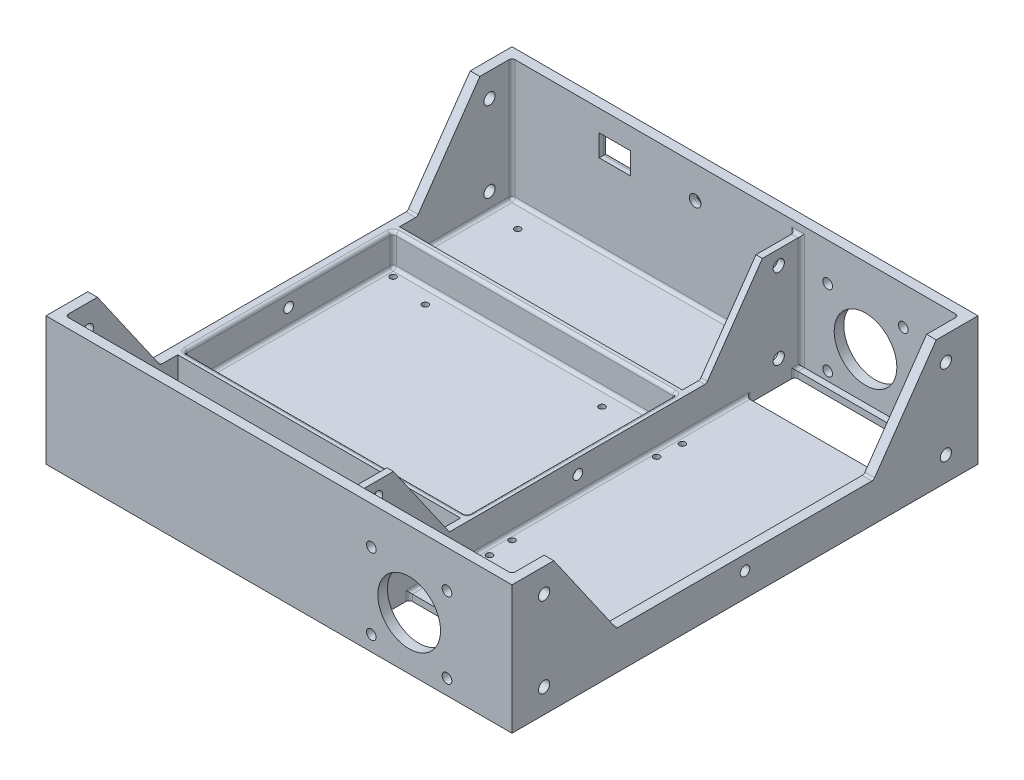
SolidWorks part; units mm, degrees
ref_plane "Спереди" through (0, 0, 0) normal (0, 0, 1) x (1, 0, 0)
ref_plane "Сверху" through (0, 0, 0) normal (0, 1, 0) x (1, 0, 0)
ref_plane "Справа" through (0, 0, 0) normal (1, 0, 0) x (0, 0, -1)
sketch "Эскиз1" plane through (0, 0, 0) normal (0, 1, 0) x (1, 0, 0)
  line L1 (-145, -145) -> (145, -145)
  line L2 (-145, -145) -> (-145, 145)
  line L3 (-145, 145) -> (145, 145)
  line L4 (145, -145) -> (145, 145)
  line L5 (0, 145) -> (0, -145) construction
  line L6 (-145, 0) -> (145, 0) construction
  point P0 (0, 0)
  dimension "D1" = 290
  dimension "D2" = 290
extrude "Бобышка-Вытянуть1" add sketch "Эскиз1" along normal blind 4
sketch "Эскиз2" plane through (0, 4, 0) normal (0, 1, 0) x (1, 0, 0)
  line L2 (145, 145) -> (145, 0.2395)
  line L5 (0, 0) -> (241.6766, 0) construction
  line L8 (145, -145) -> (145, 0.2395)
  line L11 (139, 139) -> (139, -139)
  line L13 (145, 145) -> (-145, 145) construction
  line L17 (145, 145) -> (-139, 145)
  line L18 (-139, 145) -> (-139, 139)
  line L19 (-139, 139) -> (139, 139)
  line L24 (-145, 145) -> (-145, -145) construction
  line L25 (-139, -139) -> (139, -139)
  line L30 (-139, -145) -> (-139, -139)
  line L35 (145, -145) -> (-139, -145)
  point P14 (139, 0)
  dimension "D1" = 6
  dimension "D3" = 6
  dimension "D9" = 6
extrude "Бобышка-Вытянуть2" add sketch "Эскиз2" along normal blind 76
sketch "Эскиз4" plane through (0, 4, 0) normal (0, 1, 0) x (1, 0, 0)
  line L0 (-145, -145) -> (-139, -145) construction
  line L1 (-145, 145) -> (-139, 145)
  line L2 (-145, 145) -> (-145, -145)
  line L3 (-145, -145) -> (-139, -145)
  line L4 (-139, 145) -> (-139, -145)
  dimension "D1" = 6
extrude "Бобышка-Вытянуть3" add sketch "Эскиз4" along normal up to surface (76 mm away) up to face at (1.5, 80, 0)
sketch "Эскиз17" plane through (0, 0, 145) normal (0, 0, 1) x (1, 0, 0)
  line L0 (81, 114.7773) -> (81, 33) construction
  line L1 (81, 33) -> (205.181, 33) construction
  line L2 (145, 80) -> (145, 0) construction
  line L3 (-145, 0) -> (145, 0) construction
  line L6 (57.45, 9.45) -> (104.55, 9.45) construction
  line L7 (57.45, 9.45) -> (57.45, 56.55) construction
  line L8 (57.45, 56.55) -> (104.55, 56.55) construction
  line L9 (104.55, 9.45) -> (104.55, 56.55) construction
  line L10 (81, 56.55) -> (81, 9.45) construction
  line L11 (57.45, 33) -> (104.55, 33) construction
  circle A0 centre (81, 33) radius 19.5
  circle A1 centre (57.45, 56.55) radius 3
  circle A4 centre (104.55, 56.55) radius 3
  circle A5 centre (104.55, 9.45) radius 3
  circle A6 centre (57.45, 9.45) radius 3
  dimension "D3" = 39
  dimension "D5" = 6
  dimension "D2" = 33
  dimension "D1" = 64
  dimension "D4" = 47.1
extrude "Вырез-Вытянуть12" cut sketch "Эскиз17" against normal through all both and the other way through all contours A0 | A1 | A4 | A5 | A6 region at (81, 33, 145) region at (57.45, 56.55, 145) region at (104.55, 56.55, 145) region at (104.55, 9.45, 145) region at (57.45, 9.45, 145)
sketch "Эскиз18" plane through (0, 4, 0) normal (0, 1, 0) x (1, 0, 0)
  line L0 (41, 0) -> (179.6266, 0) construction
  line L1 (-21, 118.2107) -> (-21, -110.4846) construction
  line L2 (145, -145) -> (145, 145) construction
  line L7 (37, -145) -> (41, -145)
  line L8 (37, -145) -> (37, 145)
  line L9 (37, 145) -> (41, 145)
  line L10 (41, -145) -> (41, 145)
  line L11 (39, 145) -> (39, -145) construction
  line L12 (37, 0) -> (41, 0) construction
  line L20 (145, 145) -> (-145, 145) construction
  point P16 (39, 0)
  dimension "D1" = 4
  dimension "D2" = 104
extrude "Бобышка-Вытянуть4" add sketch "Эскиз18" along normal blind 70
sketch "Эскиз19" plane through (145, 0, 0) normal (1, 0, 0) x (0, 0, -1)
  line L0 (0, 117.0161) -> (0, 24) construction
  line L1 (0, 24) -> (182.1669, 24) construction
  line L2 (-145, 0) -> (145, 0) construction
  line L3 (-80, 24) -> (80, 24)
  line L4 (80, 24) -> (119, 80)
  line L5 (-145, 80) -> (145, 80) construction
  line L6 (119, 80) -> (-119, 80)
  line L7 (145, 80) -> (145, 0) construction
  line L8 (-80, 24) -> (-119, 80)
  point P14 (0, 80)
  dimension "D1" = 24
  dimension "D2" = 26
  dimension "D3" = 160
extrude "Вырез-Вытянуть13" cut sketch "Эскиз19" against normal through all both and the other way through all
sketch "Эскиз14" plane through (0, 4, 0) normal (0, 1, 0) x (1, 0, 0)
  line L0 (81, 159.053) -> (81, -165.8467) construction
  line L2 (145, 145) -> (-145, 145) construction
  line L3 (41, 105) -> (121, 105)
  line L4 (41, 105) -> (41, 135)
  line L5 (41, 135) -> (121, 135)
  line L6 (121, 105) -> (121, 135)
  line L7 (81, 135) -> (81, 105) construction
  line L8 (41, 120) -> (121, 120) construction
  line L9 (0, 0) -> (180.733, 0) construction
  line L10 (41, -135) -> (121, -135)
  line L11 (121, -105) -> (121, -135)
  line L12 (41, -105) -> (121, -105)
  line L13 (41, -105) -> (41, -135)
  line L14 (145, 80) -> (145, -80) construction
  point P4 (81, 120)
  dimension "D1" = 64
  dimension "D2" = 80
  dimension "D3" = 30
  dimension "D4" = 10
extrude "Вырез-Вытянуть9" cut sketch "Эскиз14" against normal blind 20
sketch "Эскиз20" plane through (0, 4, 0) normal (0, 1, 0) x (1, 0, 0)
  line L0 (37, 139) -> (37, -139) construction
  line L1 (-139, 139) -> (37, 139)
  line L2 (-139, 139) -> (-139, 69)
  line L3 (-139, 69) -> (37, 69)
  line L4 (37, 139) -> (37, 69)
  line L5 (0, 0) -> (228.0193, 0) construction
  line L6 (37, -139) -> (37, -69)
  line L7 (-139, -69) -> (37, -69)
  line L8 (-139, -139) -> (-139, -69)
  line L9 (-139, -139) -> (37, -139)
  dimension "D1" = 70
extrude "Вытянуть-Тонкостенный1" add sketch "Эскиз20" along normal blind 20 thin thin type one direction wall 4
sketch "Эскиз15" plane through (-145, 0, 0) normal (-1, 0, 0) x (0, 0, 1)
  line L0 (0, 107.7828) -> (0, 40) construction
  line L1 (0, 40) -> (185.6693, 40) construction
  line L2 (-145, 0) -> (145, 0) construction
  line L3 (-171.7731, 65) -> (170.5378, 65) construction
  circle A0 centre (0, 65) radius 3
  circle A1 centre (125, 65) radius 3.5
  circle A2 centre (-125, 65) radius 3.5
  circle A3 centre (-125, 15) radius 3.5
  circle A4 centre (125, 15) radius 3.5
  circle A5 centre (0, 15) radius 3
  dimension "D3" = 6
  dimension "D4" = 125
  dimension "D1" = 40
  dimension "D2" = 25
extrude "Вырез-Вытянуть10" cut sketch "Эскиз15" against normal through all both and the other way through all
sketch "Эскиз7" plane through (0, 4, 0) normal (0, 1, 0) x (1, 0, 0)
  line L0 (0, 112.8082) -> (0, 0) construction
  line L1 (0, 0) -> (196.7673, 0) construction
  line L7 (-139, -139) -> (-139, -69) construction
  line L8 (-109, -55) -> (1, -55) construction
  line L9 (-109, -55) -> (-109, 55) construction
  line L10 (-109, 55) -> (1, 55) construction
  line L15 (1, -55) -> (1, 55) construction
  line L16 (-54, 55) -> (-54, -55) construction
  line L17 (-109, 0) -> (1, 0) construction
  line L22 (-139, 65) -> (37, 65) construction
  line L23 (-139, 65) -> (-139, -65) construction
  line L24 (139, 139) -> (139, -139) construction
  line L25 (41, 139) -> (139, 139) construction
  line L26 (90, 139) -> (90, -164.4799) construction
  line L28 (45, -45) -> (135, -45) construction
  line L29 (45, -45) -> (45, 45) construction
  line L30 (45, 45) -> (135, 45) construction
  line L31 (135, -45) -> (135, 45) construction
  line L32 (90, 45) -> (90, -45) construction
  line L33 (45, 0) -> (135, 0) construction
  line L34 (-139, 139) -> (37, 139) construction
  line L35 (-139, 119) -> (-139, 80) construction
  line L36 (-139, 99.5) -> (-51, 99.5) construction
  line L37 (-51, 99.5) -> (-51, 139) construction
  line L38 (-121, 74.5) -> (19, 74.5) construction
  line L39 (-121, 74.5) -> (-121, 124.5) construction
  line L40 (-121, 124.5) -> (19, 124.5) construction
  line L41 (19, 74.5) -> (19, 124.5) construction
  line L42 (-51, 124.5) -> (-51, 74.5) construction
  line L43 (-121, 99.5) -> (19, 99.5) construction
  circle A25 centre (-109, 55) radius 1.9
  circle A26 centre (1, 55) radius 1.9
  circle A27 centre (1, -55) radius 1.9
  circle A28 centre (-109, -55) radius 1.9
  circle A29 centre (-134, 60) radius 1.9
  circle A30 centre (-134, -60) radius 1.9
  circle A31 centre (134, 134) radius 1.9
  circle A32 centre (134, -134) radius 1.9
  circle A33 centre (134, -60) radius 1.9
  circle A34 centre (134, 60) radius 1.9
  circle A35 centre (46, -60) radius 1.9
  circle A36 centre (46, 60) radius 1.9
  circle A37 centre (45, 45) radius 1.9
  circle A38 centre (135, 45) radius 1.9
  circle A39 centre (45, -45) radius 1.9
  circle A40 centre (135, -45) radius 1.9
  circle A41 centre (-121, 124.5) radius 1.9
  circle A42 centre (-121, 74.5) radius 1.9
  circle A43 centre (19, 124.5) radius 1.9
  circle A44 centre (19, 74.5) radius 1.9
  circle A45 centre (19, -74.5) radius 1.9
  circle A46 centre (19, -124.5) radius 1.9
  circle A47 centre (-121, -74.5) radius 1.9
  circle A48 centre (-121, -124.5) radius 1.9
  point P4 (-54, 0)
  point P40 (90, 0)
  dimension "D4" = 30
  dimension "D5" = 5
  dimension "D12" = 90
  dimension "D3" = 3.8
  dimension "D6" = 5
  dimension "D7" = 120
  dimension "D8" = 5
  dimension "D9" = 5
  dimension "D10" = 268
  dimension "D17" = 93
  dimension "D18" = 46
  dimension "D19" = 134
  dimension "D20" = 134
  dimension "D1" = 110
  dimension "D2" = 110
  dimension "D11" = 90
  dimension "D13" = 140
  dimension "D14" = 50
  dimension "D15" = 60
  dimension "D16" = 134
extrude "Вырез-Вытянуть3" cut sketch "Эскиз7" against normal blind 10
fillet "Скругление1" radius 2 47 edges at (-51, 4, 69) (-51, 4, 65) (-51, 24, 65) (-139, 14, 65) (37, 14, 65) (-51, 4, -69) (-51, 4, -65) (39, 24, -80) (-139, 14, -65) (-51, 24, -65) (37, 14, -65) (41, 2, 135) (121, 2, 135) (121, 2, 105) (41, 2, 105) (121, 2, -135) (41, 2, -135) (41, 2, -105) (121, 2, -105) (142, 24, 80) (142, 24, -80) (41, 4, -137) (41, 4, 0) (41, 4, 137) (37, 4, 104) (37, 4, 0) (37, 4, -104) (39, 74, -139) (37, 39, -139) (41, 39, -139) (-139, 4, -104) (-139, 4, 0) (-139, 4, 104) (-51, 4, -139) (139, 4, 0) (-51, 4, 139) (-139, 42, 139) (139, 42, 139) (139, 42, -139) (39, 74, 139) (37, 39, 139) (41, 39, 139) (-142, 24, -80) (-139, 42, -139) (-139, 24, 0) (37, 24, 0) (-142, 24, 80)
sketch "Эскиз21" plane through (0, 0, -145) normal (0, 0, -1) x (-1, 0, 0)
  line L0 (145, 80) -> (145, 0) construction
  line L1 (-145, 80) -> (145, 80) construction
  line L3 (65.25, 53.25) -> (84.75, 53.25)
  line L4 (65.25, 53.25) -> (65.25, 66.75)
  line L5 (65.25, 66.75) -> (84.75, 66.75)
  line L6 (84.75, 53.25) -> (84.75, 66.75)
  line L7 (75, 66.75) -> (75, 53.25) construction
  line L8 (65.25, 60) -> (84.75, 60) construction
  circle A0 centre (25, 60) radius 3.6
  point P6 (75, 60)
  dimension "D1" = 7.2
  dimension "D2" = 120
  dimension "D3" = 20
  dimension "D4" = 19.5
  dimension "D5" = 13.5
  dimension "D6" = 20
  dimension "D7" = 70
extrude "Вырез-Вытянуть14" cut sketch "Эскиз21" against normal blind 10
chamfer "Фаска1" distance 2 angle 45 5 edges at (-84.75, 60, -145) (-75, 66.75, -145) (-65.25, 60, -145) (-75, 53.25, -145) (-28.6, 60, -145)
fillet "Скругление2" radius 3 5 edges at (-21.4, 60, -143) (-84.75, 60, -143) (-75, 66.75, -143) (-65.25, 60, -143) (-75, 53.25, -143)
